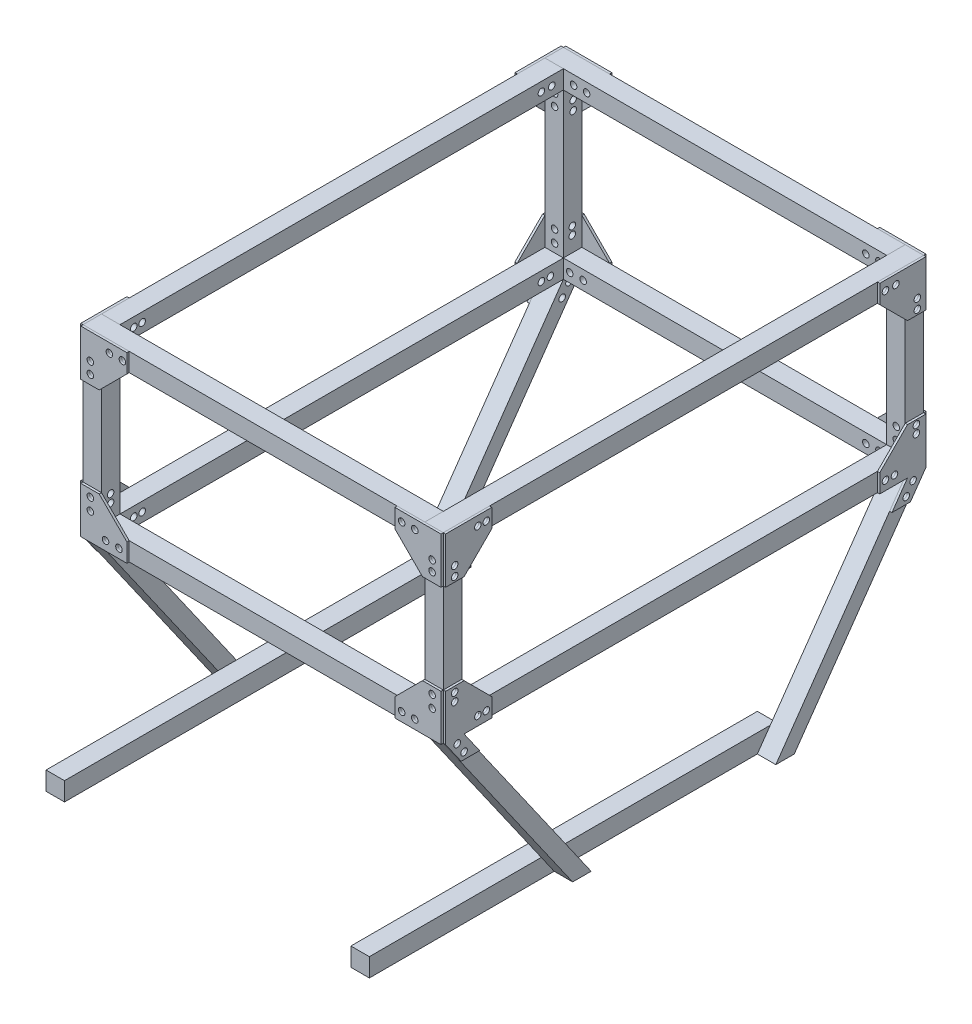
SolidWorks part; units mm, degrees
ref_plane "Front Plane" through (0, 0, 0) normal (0, 0, 1) x (1, 0, 0)
ref_plane "Top Plane" through (0, 0, 0) normal (0, 1, 0) x (1, 0, 0)
ref_plane "Right Plane" through (0, 0, 0) normal (1, 0, 0) x (0, 0, -1)
sketch "Sketch1" plane through (0, 0, 0) normal (0, 0, 1) x (1, 0, 0)
  line L1 (0, 0) -> (12.7, 0)
  line L2 (0, 0) -> (0, 12.7)
  line L3 (0, 12.7) -> (12.7, 12.7)
  line L4 (12.7, 0) -> (12.7, 12.7)
  dimension "D1" = 12.7
  dimension "D2" = 12.7
extrude "Boss-Extrude1" add sketch "Sketch1" along normal blind 304.8
sketch "Sketch3" plane through (12.7, 0, 0) normal (1, 0, 0) x (0, 0, -1)
  line L1 (0, 12.7) -> (12.7, 12.7)
  line L2 (0, 12.7) -> (0, 0)
  line L3 (0, 0) -> (12.7, 0)
  line L4 (12.7, 12.7) -> (12.7, 0)
  line L5 (-304.8, 12.7) -> (-317.5, 12.7)
  line L6 (-304.8, 12.7) -> (-304.8, 0)
  line L7 (-304.8, 0) -> (-317.5, 0)
  line L8 (-317.5, 12.7) -> (-317.5, 0)
  dimension "D1" = 12.7
  dimension "D2" = 12.7
extrude "Boss-Extrude2" add sketch "Sketch3" along normal blind 222.25 and the other way up to vertex (12.7 mm away) separate body other way up to point (0, 12.7, 0)
sketch "Sketch5" plane through (0, 0, 304.8) normal (0, 0, -1) x (-1, 0, 0)
  line L1 (-234.95, 12.7) -> (-247.65, 12.7)
  line L2 (-234.95, 12.7) -> (-234.95, 0)
  line L3 (-234.95, 0) -> (-247.65, 0)
  line L4 (-247.65, 12.7) -> (-247.65, 0)
  dimension "D1" = 12.7
extrude "Boss-Extrude3" add sketch "Sketch5" along normal blind 317.5 and the other way up to vertex (12.7 mm away) separate body other way up to point (234.95, 12.7, 317.5)
sketch "Sketch6" plane through (0, 0, 0) normal (0, -1, 0) x (1, 0, 0)
  line L0 (247.65, 317.5) -> (247.65, -12.7) construction
  line L1 (0, 317.5) -> (12.7, 317.5)
  line L2 (0, 317.5) -> (0, 304.8)
  line L3 (0, 304.8) -> (12.7, 304.8)
  line L4 (12.7, 317.5) -> (12.7, 304.8)
  line L5 (234.95, 317.5) -> (247.65, 317.5)
  line L6 (234.95, 317.5) -> (234.95, 304.8)
  line L7 (234.95, 304.8) -> (247.65, 304.8)
  line L8 (247.65, 317.5) -> (247.65, 304.8)
  line L10 (0, -12.7) -> (12.7, -12.7)
  line L11 (0, -12.7) -> (0, 0)
  line L12 (0, 0) -> (12.7, 0)
  line L13 (12.7, -12.7) -> (12.7, 0)
  line L14 (247.65, -12.7) -> (234.95, -12.7)
  line L15 (247.65, -12.7) -> (247.65, 0)
  line L16 (247.65, 0) -> (234.95, 0)
  line L17 (234.95, -12.7) -> (234.95, 0)
extrude "Boss-Extrude4" add sketch "Sketch6" along normal blind 100 separate body
sketch "Sketch8" plane through (247.65, 0, 0) normal (1, 0, 0) x (0, 0, -1)
  line L1 (-317.5, -100) -> (-304.8, -100)
  line L2 (-317.5, -100) -> (-317.5, -112.7)
  line L3 (-317.5, -112.7) -> (-304.8, -112.7)
  line L4 (-304.8, -100) -> (-304.8, -112.7)
  point P5 (-304.5323, -107.1668)
  dimension "D1" = 12.7
  dimension "D2" = 12.7
extrude "Boss-Extrude6" add sketch "Sketch8" against normal blind 247.65 separate body
sketch "Sketch9" plane through (0, 0, 304.8) normal (0, 0, -1) x (-1, 0, 0)
  line L1 (-247.65, -112.7) -> (-234.95, -112.7)
  line L2 (-247.65, -112.7) -> (-247.65, -100)
  line L3 (-247.65, -100) -> (-234.95, -100)
  line L4 (-234.95, -112.7) -> (-234.95, -100)
  line L5 (0, -112.7) -> (-12.7, -112.7)
  line L6 (0, -112.7) -> (0, -100)
  line L7 (0, -100) -> (-12.7, -100)
  line L8 (-12.7, -112.7) -> (-12.7, -100)
extrude "Boss-Extrude8" add sketch "Sketch9" along normal blind 317.5 separate body
sketch "Sketch10" plane through (234.95, 0, 0) normal (-1, 0, 0) x (0, 0, 1)
  line L1 (-12.7, -112.7) -> (0, -112.7)
  line L2 (-12.7, -112.7) -> (-12.7, -100)
  line L3 (-12.7, -100) -> (0, -100)
  line L4 (0, -112.7) -> (0, -100)
extrude "Boss-Extrude9" add sketch "Sketch10" along normal blind 222.25 separate body
sketch "Sketch12" plane through (0, 0, 0) normal (-1, 0, 0) x (0, 0, 1)
  line L0 (-12.7, -112.7) -> (0, -112.7)
  line L1 (-12.7, -112.7) -> (304.8, -112.7) construction
  line L2 (0, -112.7) -> (88.9264, -239.7)
  line L3 (88.9264, -239.7) -> (76.2264, -239.7)
  line L4 (76.2264, -239.7) -> (-12.7, -112.7)
  dimension "D1" = 127
  dimension "D2" = 12.7
  dimension "D3" = 12.7
  dimension "D4" = 55
extrude "Boss-Extrude11" add sketch "Sketch12" against normal blind 12.7 separate body
sketch "Sketch13" plane through (0, 0, 0) normal (-1, 0, 0) x (0, 0, 1)
  line L0 (317.5, -112.7) -> (304.8, -112.7)
  line L1 (304.8, -112.7) -> (215.8736, -239.7)
  line L2 (215.8736, -239.7) -> (228.5736, -239.7)
  line L3 (228.5736, -239.7) -> (317.5, -112.7)
  dimension "D1" = 127
  dimension "D2" = 12.7
  dimension "D3" = 55
extrude "Boss-Extrude12" add sketch "Sketch13" against normal blind 12.7 separate body
sketch "Sketch14" plane through (247.65, 0, 0) normal (1, 0, 0) x (0, 0, -1)
  line L0 (-317.5, -112.7) -> (-228.5736, -239.7)
  line L1 (-228.5736, -239.7) -> (-215.8736, -239.7)
  line L2 (-215.8736, -239.7) -> (-304.8, -112.7)
  line L3 (-304.8, -112.7) -> (-317.5, -112.7)
  line L4 (-88.9264, -239.7) -> (-76.2264, -239.7)
  line L5 (-76.2264, -239.7) -> (12.7, -112.7)
  line L6 (12.7, -112.7) -> (0, -112.7)
  line L7 (0, -112.7) -> (-88.9264, -239.7)
extrude "Boss-Extrude13" add sketch "Sketch14" against normal blind 12.7 separate body
sketch "Sketch15" plane through (12.7, 0, 0) normal (1, 0, 0) x (0, 0, -1)
  line L0 (-76.2264, -239.7) -> (-76.2264, -227)
  line L1 (-76.2264, -227) -> (-355.6264, -227)
  line L2 (-355.6264, -227) -> (-355.6264, -239.7)
  line L3 (-355.6264, -239.7) -> (-76.2264, -239.7)
  dimension "D1" = 12.7
  dimension "D2" = 279.4
extrude "Boss-Extrude15" add sketch "Sketch15" along normal blind 12.7 separate body
sketch "Sketch16" plane through (234.95, 0, 0) normal (-1, 0, 0) x (0, 0, 1)
  line L0 (76.2264, -239.7) -> (76.2264, -227)
  line L1 (76.2264, -227) -> (355.6264, -227)
  line L2 (355.6264, -227) -> (355.6264, -239.7)
  line L3 (355.6264, -239.7) -> (76.2264, -239.7)
  dimension "D1" = 12.7
  dimension "D2" = 279.4
extrude "Boss-Extrude16" add sketch "Sketch16" along normal blind 12.7 separate body
sketch "Sketch17" plane through (0, 0, 0) normal (-1, 0, 0) x (0, 0, 1)
  line L0 (-12.7, 12.7) -> (19.05, 12.7)
  line L1 (304.8, 12.7) -> (0, 12.7) construction
  line L2 (19.05, 12.7) -> (19.05, 0)
  line L3 (304.8, 0) -> (0, 0) construction
  line L4 (19.05, 0) -> (0, -19.05)
  line L5 (0, -100) -> (0, 0) construction
  line L6 (0, -19.05) -> (-12.7, -19.05)
  line L7 (-12.7, -100) -> (-12.7, 0) construction
  line L8 (-12.7, -19.05) -> (-12.7, 12.7)
  line L9 (317.5, 12.7) -> (285.75, 12.7)
  line L10 (285.75, 12.7) -> (285.75, 0)
  line L11 (285.75, 0) -> (304.8, -19.05)
  line L12 (304.8, -100) -> (304.8, 0) construction
  line L13 (304.8, -19.05) -> (317.5, -19.05)
  line L14 (317.5, -100) -> (317.5, 0) construction
  line L15 (317.5, -19.05) -> (317.5, 12.7)
  line L16 (-12.7, -112.7) -> (-12.7, -80.95)
  line L17 (-12.7, -80.95) -> (0, -80.95)
  line L18 (0, -80.95) -> (19.05, -100)
  line L19 (-12.7, -100) -> (304.8, -100) construction
  line L20 (19.05, -100) -> (19.05, -112.7)
  line L21 (-12.7, -112.7) -> (304.8, -112.7) construction
  line L23 (317.5, -112.7) -> (317.5, -80.95)
  line L24 (317.5, -80.95) -> (304.8, -80.95)
  line L25 (304.8, -80.95) -> (285.75, -100)
  line L26 (285.75, -100) -> (285.75, -112.7)
  line L28 (-12.7, -112.7) -> (-2.0288, -127.94)
  line L29 (-12.7, -112.7) -> (76.2264, -239.7) construction
  line L30 (-2.0288, -127.94) -> (10.6712, -127.94)
  line L31 (88.9264, -239.7) -> (0, -112.7) construction
  line L32 (10.6712, -127.94) -> (0, -112.7)
  line L33 (0, -112.7) -> (19.05, -112.7)
  line L34 (317.5, -112.7) -> (306.8288, -127.94)
  line L35 (228.5736, -239.7) -> (317.5, -112.7) construction
  line L36 (306.8288, -127.94) -> (294.1288, -127.94)
  line L37 (304.8, -112.7) -> (215.8736, -239.7) construction
  line L38 (294.1288, -127.94) -> (304.8, -112.7)
  line L39 (304.8, -112.7) -> (285.75, -112.7)
  circle A0 centre (-6.7847, -15.7208) radius 2.25
  circle A1 centre (-6.7847, -9.1845) radius 2.25
  circle A2 centre (15.1208, 6.3614) radius 2.25
  circle A3 centre (7.9661, 6.3614) radius 2.25
  circle A4 centre (-3.8386, -116.1836) radius 2.25
  circle A5 centre (0.8299, -123.4038) radius 2.25
  circle A6 centre (-6.1056, -84.0258) radius 2.25
  circle A7 centre (-6.1056, -89.426) radius 2.25
  circle A8 centre (15.1208, -106.4791) radius 2.25
  circle A9 centre (8.9324, -106.4791) radius 2.25
  circle A10 centre (289.5093, 6.3614) radius 2.25
  circle A11 centre (295.3157, 6.3614) radius 2.25
  circle A12 centre (311.2568, -15.7208) radius 2.25
  circle A13 centre (311.2568, -9.1845) radius 2.25
  circle A14 centre (311.2568, -84.6779) radius 2.25
  circle A16 centre (289.5093, -106.4791) radius 2.25
  circle A17 centre (295.3157, -106.4791) radius 2.25
  circle A18 centre (309.4689, -116.1836) radius 2.25
  circle A19 centre (304.8, -123.4038) radius 2.25
  circle A20 centre (311.2568, -90.3243) radius 2.25
  point P96 (0, 0)
  dimension "D7" = 4.5
  dimension "D8" = 4.5
  dimension "D9" = 4.5
  dimension "D10" = 4.5
  dimension "D11" = 4.5
  dimension "D12" = 4.5
  dimension "D13" = 4.5
  dimension "D14" = 4.5
  dimension "D15" = 4.5
  dimension "D16" = 4.5
  dimension "D17" = 4.5
  dimension "D18" = 4.5
  dimension "D19" = 4.5
  dimension "D1" = 31.75
  dimension "D2" = 31.75
  dimension "D3" = 31.75
  dimension "D4" = 31.75
  dimension "D5" = 15.24
  dimension "D6" = 15.24
extrude "Boss-Extrude17" add sketch "Sketch17" along normal blind 1.5875 separate body
sketch "Sketch18" plane through (0, 0, 317.5) normal (0, 0, 1) x (1, 0, 0)
  line L0 (0, 12.7) -> (31.75, 12.7)
  line L1 (0, 12.7) -> (234.95, 12.7) construction
  line L2 (31.75, 12.7) -> (31.75, 0)
  line L3 (0, 0) -> (234.95, 0) construction
  line L4 (31.75, 0) -> (12.7, -19.05)
  line L5 (12.7, -100) -> (12.7, 0) construction
  line L6 (12.7, -19.05) -> (0, -19.05)
  line L7 (0, -100) -> (0, 0) construction
  line L8 (0, -19.05) -> (0, 12.7)
  line L9 (247.65, 12.7) -> (247.65, -19.05)
  line L10 (247.65, -100) -> (247.65, 0) construction
  line L11 (247.65, -19.05) -> (234.95, -19.05)
  line L12 (234.95, -100) -> (234.95, 0) construction
  line L13 (234.95, -19.05) -> (215.9, 0)
  line L14 (215.9, 0) -> (215.9, 12.7)
  line L15 (215.9, 12.7) -> (247.65, 12.7)
  line L16 (0, -112.7) -> (31.75, -112.7)
  line L17 (0, -112.7) -> (247.65, -112.7) construction
  line L18 (31.75, -112.7) -> (31.75, -100)
  line L19 (0, -100) -> (247.65, -100) construction
  line L20 (31.75, -100) -> (12.7, -80.95)
  line L21 (12.7, -80.95) -> (0, -80.95)
  line L22 (0, -80.95) -> (0, -112.7)
  line L23 (247.65, -112.7) -> (247.65, -80.95)
  line L24 (247.65, -80.95) -> (234.95, -80.95)
  line L25 (234.95, -80.95) -> (215.9, -100)
  line L26 (215.9, -100) -> (215.9, -112.7)
  line L27 (215.9, -112.7) -> (247.65, -112.7)
  dimension "D1" = 31.75
  dimension "D2" = 31.75
  dimension "D3" = 31.75
  dimension "D4" = 31.75
  dimension "D5" = 31.75
  dimension "D6" = 31.75
  dimension "D7" = 31.75
extrude "Boss-Extrude18" add sketch "Sketch18" along normal blind 1.5875 separate body
sketch "Sketch19" plane through (247.65, 0, 0) normal (1, 0, 0) x (0, 0, -1)
  line L0 (-317.5, 12.7) -> (-285.75, 12.7)
  line L1 (-317.5, 12.7) -> (12.7, 12.7) construction
  line L2 (-285.75, 12.7) -> (-285.75, 0)
  line L3 (-317.5, 0) -> (12.7, 0) construction
  line L4 (-285.75, 0) -> (-304.8, -19.05)
  line L5 (-304.8, -100) -> (-304.8, 0) construction
  line L6 (-304.8, -19.05) -> (-317.5, -19.05)
  line L7 (-317.5, -100) -> (-317.5, 0) construction
  line L8 (-317.5, -19.05) -> (-317.5, 12.7)
  line L9 (12.7, 12.7) -> (12.7, -19.05)
  line L10 (12.7, -19.05) -> (0, -19.05)
  line L11 (0, -100) -> (0, 0) construction
  line L12 (0, -19.05) -> (-19.05, 0)
  line L13 (-19.05, 0) -> (-19.05, 12.7)
  line L14 (-19.05, 12.7) -> (12.7, 12.7)
  line L16 (12.7, -112.7) -> (-304.8, -112.7) construction
  line L17 (-285.75, -112.7) -> (-285.75, -100)
  line L18 (12.7, -100) -> (-304.8, -100) construction
  line L19 (-285.75, -100) -> (-304.8, -80.95)
  line L20 (-304.8, -80.95) -> (-317.5, -80.95)
  line L21 (-317.5, -80.95) -> (-317.5, -112.7)
  line L22 (12.7, -112.7) -> (12.7, -80.95)
  line L23 (12.7, -100) -> (12.7, 0) construction
  line L24 (12.7, -80.95) -> (0, -80.95)
  line L25 (0, -80.95) -> (-19.05, -100)
  line L26 (-19.05, -100) -> (-19.05, -112.7)
  line L28 (-317.5, -112.7) -> (-306.8288, -127.94)
  line L29 (-317.5, -112.7) -> (-228.5736, -239.7) construction
  line L30 (-306.8288, -127.94) -> (-294.1288, -127.94)
  line L31 (-215.8736, -239.7) -> (-304.8, -112.7) construction
  line L32 (-294.1288, -127.94) -> (-304.8, -112.7)
  line L33 (-304.8, -112.7) -> (-285.75, -112.7)
  line L34 (12.7, -112.7) -> (2.0288, -127.94)
  line L35 (-76.2264, -239.7) -> (12.7, -112.7) construction
  line L36 (2.0288, -127.94) -> (-10.6712, -127.94)
  line L37 (0, -112.7) -> (-88.9264, -239.7) construction
  line L38 (-10.6712, -127.94) -> (0, -112.7)
  line L39 (0, -112.7) -> (-19.05, -112.7)
  dimension "D1" = 31.75
  dimension "D2" = 31.75
  dimension "D3" = 15.24
  dimension "D4" = 15.24
extrude "Boss-Extrude19" add sketch "Sketch19" along normal blind 1.5875 separate body
sketch "Sketch20" plane through (0, 0, -12.7) normal (0, 0, -1) x (-1, 0, 0)
  line L0 (-247.65, 12.7) -> (-215.9, 12.7)
  line L1 (0, 12.7) -> (-234.95, 12.7) construction
  line L2 (-215.9, 12.7) -> (-215.9, 0)
  line L3 (0, 0) -> (-234.95, 0) construction
  line L4 (-215.9, 0) -> (-234.95, -20.3448)
  line L5 (-234.95, -100) -> (-234.95, 0) construction
  line L6 (-234.95, -20.3448) -> (-247.65, -19.05)
  line L7 (-247.65, -100) -> (-247.65, 0) construction
  line L8 (-247.65, -19.05) -> (-247.65, 12.7) construction
  line L9 (-247.65, -19.05) -> (-247.65, 12.7)
  line L10 (0, 12.7) -> (-31.75, 12.7)
  line L11 (-31.75, 12.7) -> (-31.75, 0)
  line L13 (-31.75, 0) -> (-12.7, -19.05)
  line L14 (-12.7, -19.05) -> (0, -19.05)
  line L15 (-247.65, -112.7) -> (-215.9, -112.7)
  line L16 (-12.7, -112.7) -> (-234.95, -112.7) construction
  line L17 (-215.9, -112.7) -> (-215.9, -100)
  line L18 (-12.7, -100) -> (-234.95, -100) construction
  line L19 (-215.9, -100) -> (-234.95, -80.95)
  line L20 (-234.95, -80.95) -> (-247.65, -80.95)
  line L21 (-247.65, -80.95) -> (-247.65, -112.7)
  line L22 (0, -112.7) -> (0, -80.95)
  line L23 (0, -80.95) -> (-12.7, -80.95)
  line L24 (-12.7, -100) -> (-12.7, 0) construction
  line L25 (-12.7, -80.95) -> (-31.75, -100)
  line L26 (-31.75, -100) -> (-31.75, -112.7)
  line L27 (-31.75, -112.7) -> (0, -112.7)
  line L28 (0, -19.05) -> (0, 12.7)
  circle A0 centre (-220.6293, 6.3497) radius 2.25
  circle A1 centre (-229.6227, 6.3497) radius 2.25
  circle A2 centre (-241.5436, -12.822) radius 2.25
  circle A3 centre (-241.5436, -5.7894) radius 2.25
  circle A4 centre (-241.5436, -85.8523) radius 2.25
  circle A5 centre (-241.5436, -94.1692) radius 2.25
  circle A6 centre (-229.6227, -106.4874) radius 2.25
  circle A7 centre (-220.6293, -106.4874) radius 2.25
  circle A8 centre (-28.6709, 6.3497) radius 2.25
  circle A9 centre (-19.6968, 6.3497) radius 2.25
  circle A10 centre (-6.6214, -4.8902) radius 2.25
  circle A11 centre (-6.6214, -12.822) radius 2.25
  circle A12 centre (-6.6214, -85.8523) radius 2.25
  circle A13 centre (-6.6214, -94.1692) radius 2.25
  circle A14 centre (-26.2877, -106.4874) radius 2.25
  circle A15 centre (-17.0622, -106.4874) radius 2.25
  dimension "D3" = 4.5
  dimension "D1" = 31.75
  dimension "D2" = 31.75
extrude "Boss-Extrude20" add sketch "Sketch20" along normal blind 1.5875 separate body
extrude "Cut-Extrude1" cut sketch "Sketch17<4>" against normal through all contours A2 | A3 | A1 | A0 region at (0, -15.7208, -6.7847) region at (0, -9.1845, -6.7847) region at (0, 6.3614, 15.1208) region at (0, 6.3614, 7.9661)
sketch "Sketch17<4>" plane through (0, 0, 0) normal (-1, 0, 0) x (0, 0, 1) same geometry as "Sketch17"
extrude "Cut-Extrude4" cut sketch "Sketch17<6>" against normal through all contours A6 | A7 | A9 | A8 | A4 | A5 region at (0, -116.1836, -3.8386) region at (0, -123.4038, 0.8299) region at (0, -84.0258, -6.1056) region at (0, -89.426, -6.1056) region at (0, -106.4791, 15.1208) region at (0, -106.4791, 8.9324)
sketch "Sketch17<6>" plane through (0, 0, 0) normal (-1, 0, 0) x (0, 0, 1) same geometry as "Sketch17"
extrude "Cut-Extrude5" cut sketch "Sketch17<7>" against normal through all contours A10 | A11 | A13 | A12 | A14 | A20 | A17 | A16 | A18 | A19 region at (0, 6.3614, 289.5093) region at (0, 6.3614, 295.3157) region at (0, -15.7208, 311.2568) region at (0, -9.1845, 311.2568) region at (0, -84.6779, 311.2568) region at (0, -106.4791, 289.5093) region at (0, -106.4791, 295.3157) region at (0, -116.1836, 309.4689) region at (0, -123.4038, 304.8) region at (0, -90.3243, 311.2568)
sketch "Sketch17<7>" plane through (0, 0, 0) normal (-1, 0, 0) x (0, 0, 1) same geometry as "Sketch17"
extrude "Cut-Extrude6" cut sketch "Sketch20<2>" against normal through all contours A1 | A0 | A3 | A2 | A4 | A5 | A6 | A7 | A8 | A9 | A10 | A11 | A12 | A13 | A15 | A14 region at (220.6293, 6.3497, -12.7) region at (229.6227, 6.3497, -12.7) region at (241.5436, -12.822, -12.7) region at (241.5436, -5.7894, -12.7) region at (241.5436, -85.8523, -12.7) region at (241.5436, -94.1692, -12.7) region at (229.6227, -106.4874, -12.7) region at (220.6293, -106.4874, -12.7) region at (28.6709, 6.3497, -12.7) region at (19.6968, 6.3497, -12.7) region at (6.6214, -4.8902, -12.7) region at (6.6214, -12.822, -12.7) region at (6.6214, -85.8523, -12.7) region at (6.6214, -94.1692, -12.7) region at (26.2877, -106.4874, -12.7) region at (17.0622, -106.4874, -12.7)
sketch "Sketch20<2>" plane through (0, 0, -12.7) normal (0, 0, -1) x (-1, 0, 0) same geometry as "Sketch20"
